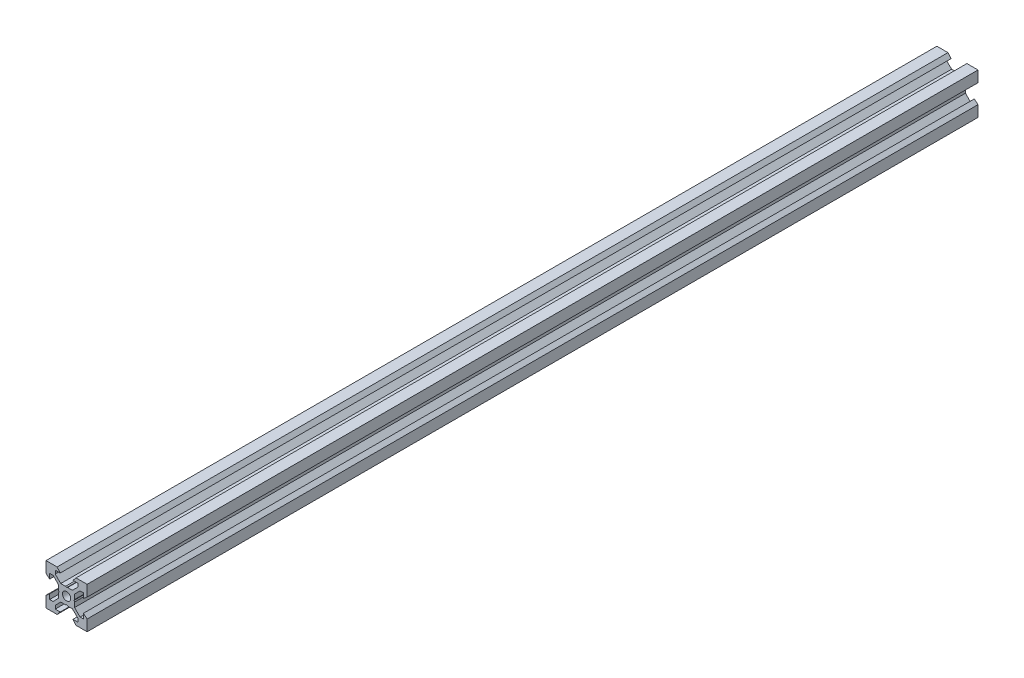
SolidWorks part; units mm, degrees
ref_plane "Front Plane" through (0, 0, 0) normal (0, 0, 1) x (1, 0, 0)
ref_plane "Top Plane" through (0, 0, 0) normal (0, 1, 0) x (1, 0, 0)
ref_plane "Right Plane" through (0, 0, 0) normal (1, 0, 0) x (0, 0, -1)
sketch "Sketch1" plane through (0, 0, 0) normal (0, 0, 1) x (1, 0, 0)
  line L0 (10, 10) -> (4.6104, 10) construction
  line L1 (10, 10) -> (10, 4.6104) construction
  line L2 (10, -10) -> (10, -4.6104) construction
  line L3 (10, -10) -> (4.6104, -10) construction
  line L4 (10, 10) -> (10, 4.6104)
  line L5 (6.5607, 5.5) -> (8.2, 5.5)
  line L6 (5.5, 8.2) -> (5.5, 6.5607)
  line L7 (10, 10) -> (4.6104, 10)
  line L8 (10, 10) -> (10, 4.6104)
  line L9 (6.5607, 5.5) -> (3.9, 2.8393)
  line L10 (5.5, 6.5607) -> (2.8393, 3.9)
  line L11 (10, 4.6104) -> (8.2, 3.1)
  line L12 (4.6104, 10) -> (3.1, 8.2)
  line L13 (8.2, 3.1) -> (8.2, 5.5)
  line L14 (3.1, 8.2) -> (5.5, 8.2)
  line L15 (-6.5607, 5.5) -> (-8.2, 5.5)
  line L16 (6.5607, -5.5) -> (8.2, -5.5)
  line L17 (3.1, -8.2) -> (5.5, -8.2)
  line L18 (8.2, -3.1) -> (8.2, -5.5)
  line L19 (4.6104, -10) -> (3.1, -8.2)
  line L20 (10, -4.6104) -> (8.2, -3.1)
  line L21 (0.5196, -3.9) -> (0, -3.6)
  line L22 (0.5196, 3.9) -> (0, 3.6)
  line L23 (3.6, 0) -> (3.9, -0.5196)
  line L24 (3.9, 0.5196) -> (3.6, 0)
  line L25 (3.9, 0.5196) -> (3.9, 2.8393)
  line L26 (2.8393, 3.9) -> (0.5196, 3.9)
  line L27 (3.9, -2.8393) -> (3.9, -0.5196)
  line L28 (2.8393, -3.9) -> (0.5196, -3.9)
  line L29 (5.5, -6.5607) -> (2.8393, -3.9)
  line L30 (6.5607, -5.5) -> (3.9, -2.8393)
  line L31 (10, -10) -> (10, -4.6104)
  line L32 (10, -10) -> (4.6104, -10)
  line L33 (5.5, -8.2) -> (5.5, -6.5607)
  line L34 (-6.5607, -5.5) -> (-8.2, -5.5)
  line L35 (10, -10) -> (10, -4.6104)
  line L36 (0, 0) -> (0, 8.2) construction
  line L37 (-10, -10) -> (-4.6104, -10) construction
  line L38 (-10, -10) -> (-10, -4.6104) construction
  line L39 (-10, 10) -> (-10, 4.6104) construction
  line L40 (-10, 10) -> (-4.6104, 10) construction
  line L41 (-10, -10) -> (-10, -4.6104)
  line L43 (-5.5, -8.2) -> (-5.5, -6.5607)
  line L44 (-10, -10) -> (-4.6104, -10)
  line L45 (-10, -10) -> (-10, -4.6104)
  line L46 (-6.5607, -5.5) -> (-3.9, -2.8393)
  line L47 (-5.5, -6.5607) -> (-2.8393, -3.9)
  line L48 (-2.8393, -3.9) -> (-0.5196, -3.9)
  line L49 (-3.9, -2.8393) -> (-3.9, -0.5196)
  line L50 (-2.8393, 3.9) -> (-0.5196, 3.9)
  line L51 (-3.9, 0.5196) -> (-3.9, 2.8393)
  line L52 (-3.9, 0.5196) -> (-3.6, 0)
  line L53 (-3.6, 0) -> (-3.9, -0.5196)
  line L54 (-0.5196, 3.9) -> (0, 3.6)
  line L55 (-0.5196, -3.9) -> (0, -3.6)
  line L56 (-10, -4.6104) -> (-8.2, -3.1)
  line L57 (-4.6104, -10) -> (-3.1, -8.2)
  line L58 (-8.2, -3.1) -> (-8.2, -5.5)
  line L59 (-3.1, -8.2) -> (-5.5, -8.2)
  line L60 (-10, -10) -> (10, -10) construction
  line L61 (-10, -10) -> (-10, 10) construction
  line L62 (-3.1, 8.2) -> (-5.5, 8.2)
  line L63 (-8.2, 3.1) -> (-8.2, 5.5)
  line L64 (-4.6104, 10) -> (-3.1, 8.2)
  line L65 (-10, 4.6104) -> (-8.2, 3.1)
  line L66 (-5.5, 6.5607) -> (-2.8393, 3.9)
  line L67 (-6.5607, 5.5) -> (-3.9, 2.8393)
  line L68 (-10, 10) -> (-10, 4.6104)
  line L69 (-10, 10) -> (-4.6104, 10)
  line L70 (-5.5, 8.2) -> (-5.5, 6.5607)
  line L71 (-10, 10) -> (10, 10) construction
  line L72 (-10, 10) -> (-10, 4.6104)
  line L73 (10, -10) -> (10, 10) construction
  line L74 (-10, -10) -> (10, 10) construction
  line L75 (-10, 10) -> (10, -10) construction
  circle A0 centre (0, 0) radius 2
  dimension "D7" = 4
  dimension "D1" = 20
  dimension "D2" = 5.3896
  dimension "D3" = 4.5
  dimension "D4" = 50
  dimension "D5" = 1.8
  dimension "D6" = 1.5104
  dimension "D8" = 5.5
  dimension "D9" = 120
  dimension "D10" = 0.3
  dimension "D11" = 2.3197
  dimension "D12" = 7.8
  dimension "D13" = 7.8
  dimension "D14" = 1.5
  dimension "D15" = 2.6607
extrude "Boss-Extrude1" add sketch "Sketch1" along normal mid plane 433.21 contours L70 L62 L64 L69 L68 L65 L63 L15 L67 L51 L52 L53 L49 L46 L34 L58 L56 L41 L44 L57 L59 L43 L47 L48 L55 L21 L28 L29 L33 L17 L19 L32 L31 L20 L18 L16 L30 L27 L23 L24 L25 L9 L5 L13 L11 L4 L7 L12 L14 L6 L10 region at (9.7172, 7.3052, 0)
